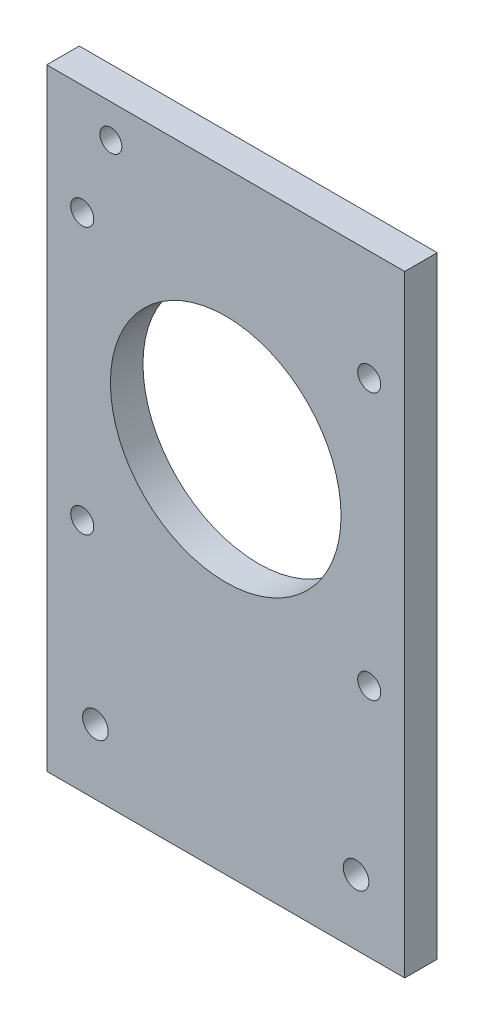
SolidWorks part; units mm, degrees
ref_plane "Front Plane" through (0, 0, 0) normal (0, 0, 1) x (1, 0, 0)
ref_plane "Top Plane" through (0, 0, 0) normal (0, 1, 0) x (1, 0, 0)
ref_plane "Right Plane" through (0, 0, 0) normal (1, 0, 0) x (0, 0, -1)
sketch "Sketch2" plane through (0, 0, 0) normal (0, 0, 1) x (1, 0, 0)
  line L0 (-55, 62.4) -> (55, 62.4) construction
  line L1 (-34.925, 0) -> (34.925, 0)
  line L2 (-34.925, 0) -> (-34.925, 71.9)
  line L3 (-34.925, 71.9) -> (34.925, 71.9) construction
  line L4 (34.925, 0) -> (34.925, 71.9)
  line L5 (0, 62.4) -> (0, 0) construction
  line L6 (0, 62.4) -> (0, 71.9) construction
  line L7 (-34.925, 25.4) -> (34.925, 25.4) construction
  line L10 (34.925, 104.4) -> (-34.925, 104.4) construction
  line L11 (34.925, 71.9) -> (34.925, 104.4)
  line L12 (34.925, 104.4) -> (-34.925, 104.4) construction
  line L13 (-34.925, 104.4) -> (-34.925, 71.9)
  line L14 (34.925, 104.4) -> (34.925, 119.4)
  line L15 (34.925, 119.4) -> (-34.925, 119.4)
  line L16 (-34.925, 104.4) -> (-34.925, 119.4)
  line L17 (-34.925, 25.4) -> (34.925, 25.4) construction
  circle A0 centre (-55, 62.4) radius 3 construction
  circle A1 centre (55, 62.4) radius 3 construction
  circle A2 centre (-55, 62.4) radius 15 construction
  circle A3 centre (55, 62.4) radius 15 construction
  circle A6 centre (0, 71.9) radius 22.5
  circle A7 centre (-55, 62.4) radius 15.6 construction
  point P6 (0, 0)
  dimension "D1" = 6
  dimension "D2" = 30
  dimension "D5" = 45
  dimension "D9" = 15
  dimension "D3" = 110
  dimension "D4" = 9.5
  dimension "D6" = 69.85
  dimension "D7" = 46.5
  dimension "D8" = 32.5
  dimension "D10" = 25.4
  dimension "D11" = 0.6
extrude "Boss-Extrude1" add sketch "Sketch2" along normal mid plane 6.35
sketch "Sketch3" plane through (0, 0, 3.175) normal (0, 0, 1) x (1, 0, 0)
  line L0 (34.925, 119.4) -> (-34.925, 119.4) construction
  line L1 (-34.925, 0) -> (-25.425, 0) construction
  line L2 (-34.925, 0) -> (-34.925, 12.7) construction
  line L3 (-34.925, 12.7) -> (-25.425, 12.7) construction
  line L4 (-25.425, 0) -> (-25.425, 12.7) construction
  line L5 (34.925, 0) -> (25.425, 0) construction
  line L6 (34.925, 0) -> (34.925, 12.7) construction
  line L7 (34.925, 12.7) -> (25.425, 12.7) construction
  line L8 (25.425, 0) -> (25.425, 12.7) construction
  line L9 (-34.925, 119.4) -> (-34.925, 0) construction
  circle A0 centre (-25.425, 12.7) radius 2.5
  circle A1 centre (25.425, 12.7) radius 2.5
  circle A2 centre (-22.425, 112.9) radius 2.15
  dimension "D1" = 12.7
  dimension "D2" = 5
  dimension "D4" = 4.3
  dimension "D5" = 6.5
  dimension "D3" = 9.5
  dimension "D6" = 12.5
extrude "Cut-Extrude1" cut sketch "Sketch3" against normal through all both and the other way through all
sketch "Sketch4" plane through (0, 0, -3.175) normal (0, 0, -1) x (-1, 0, 0)
  circle A0 centre (28, 45.9) radius 2.25 construction
  circle A1 centre (-28, 45.9) radius 2.25 construction
  circle A2 centre (28, 97.9) radius 2.25 construction
  circle A3 centre (-28, 97.9) radius 2.25 construction
  circle A4 centre (28, 45.9) radius 2.25
  circle A5 centre (-28, 45.9) radius 2.25
  circle A6 centre (28, 97.9) radius 2.25
  circle A7 centre (-28, 97.9) radius 2.25
extrude "Cut-Extrude2" cut sketch "Sketch4" against normal through all both and the other way through all
